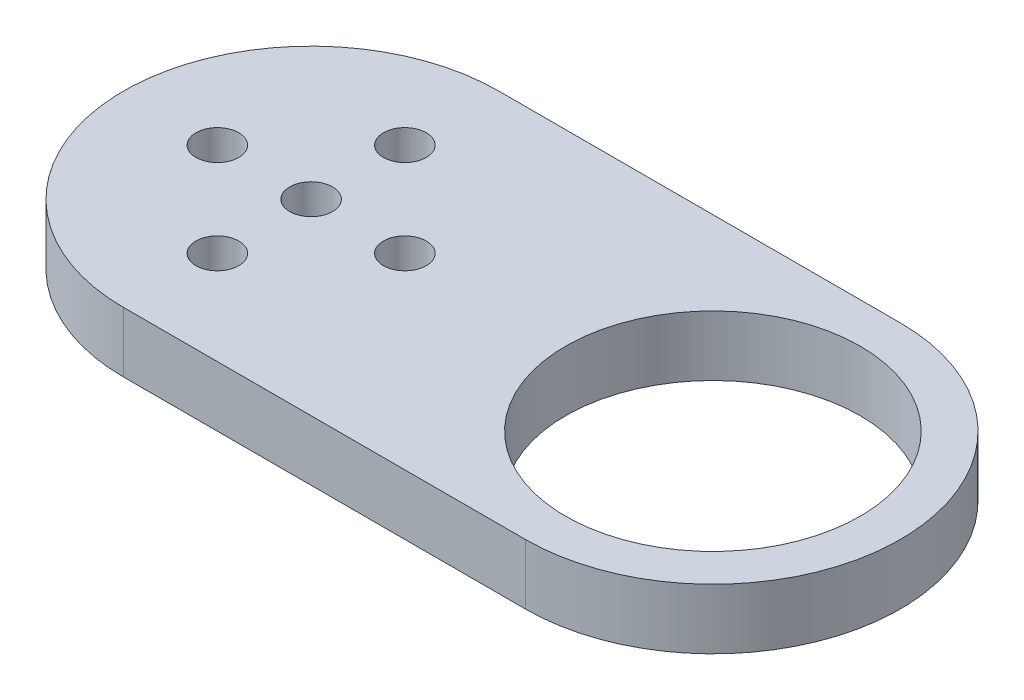
SolidWorks part; units mm, degrees
ref_plane "Front Plane" through (0, 0, 0) normal (0, 0, 1) x (1, 0, 0)
ref_plane "Top Plane" through (0, 0, 0) normal (0, 1, 0) x (1, 0, 0)
ref_plane "Right Plane" through (0, 0, 0) normal (1, 0, 0) x (0, 0, -1)
sketch "Sketch2" plane through (0, 0, 0) normal (0, 1, 0) x (1, 0, 0)
  line L0 (15, 0) -> (-15, 0) construction
  line L1 (15, 14) -> (-15, 14)
  line L2 (15, -14) -> (-15, -14)
  arc A0 (15, 14) -> (15, -14) centre (15, 0) cw
  arc A1 (-15, 14) -> (-15, -14) centre (-15, 0) ccw
  point P4 (0, 0)
  dimension "D1" = 30
  dimension "D2" = 14
  dimension "D3" = 14
extrude "Boss-Extrude1" add sketch "Sketch2" along normal blind 4.5
sketch "Sketch4" plane through (0, 4.5, 0) normal (0, 1, 0) x (1, 0, 0)
  line L0 (-15, 0) -> (-8, 0) construction
  line L1 (15, 0) -> (-15, 0) construction
  line L2 (-15, 0) -> (-8, 0) construction
  circle A0 centre (-15, 0) radius 1.6
  circle A1 centre (-8, 0) radius 1.6
  circle A2 centre (-15, -7) radius 1.6
  circle A3 centre (-22, 0) radius 1.6
  circle A4 centre (-15, 7) radius 1.6
  dimension "D1" = 3.2
  dimension "D2" = 7
  dimension "D3" = 4
extrude "Servo horn holes" cut sketch "Sketch4" against normal through all
sketch "Sketch5" plane through (0, 0, 0) normal (0, -1, 0) x (-1, 0, 0)
  circle A0 centre (-15, 0) radius 11
  dimension "D1" = 22
extrude "Bearing press fit" cut sketch "Sketch5" against normal through all
